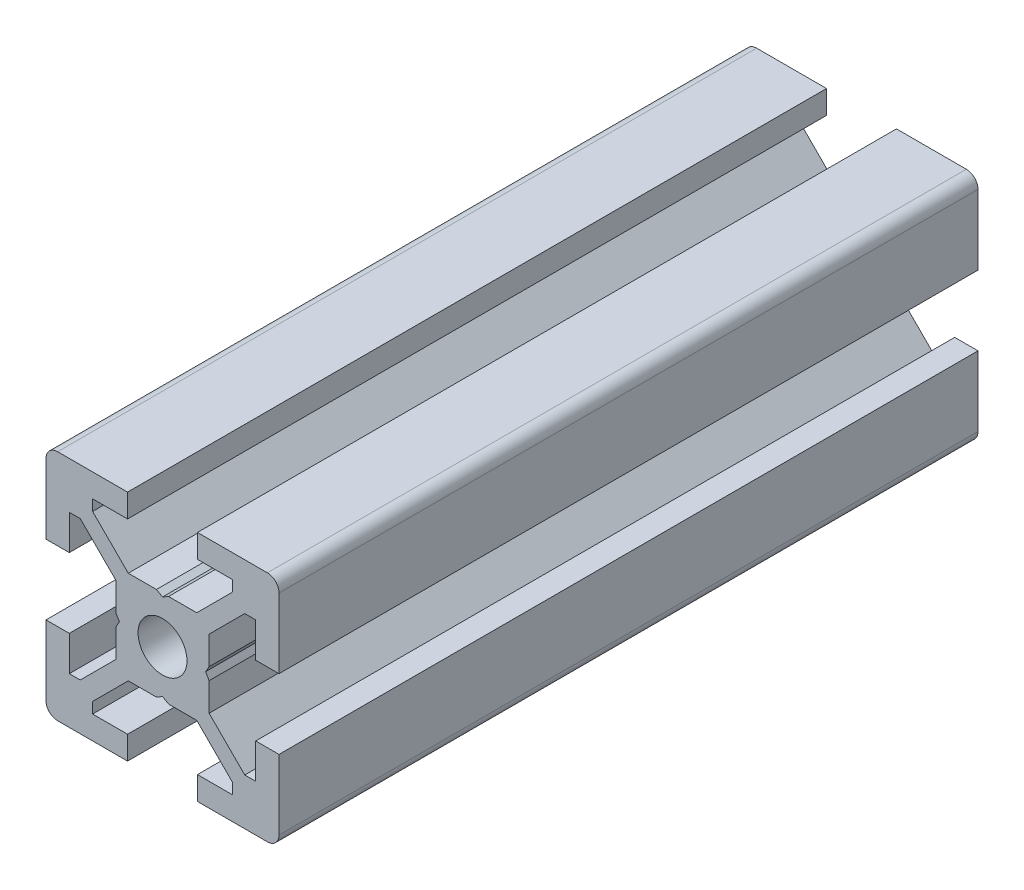
SolidWorks part; units mm, degrees
ref_plane "Front Plane" through (0, 0, 0) normal (0, 0, 1) x (1, 0, 0)
ref_plane "Top Plane" through (0, 0, 0) normal (0, 1, 0) x (1, 0, 0)
ref_plane "Right Plane" through (0, 0, 0) normal (1, 0, 0) x (0, 0, -1)
ref_plane "Plane1" through (0, 0, 0) normal (0, 0, 1) x (1, 0, 0)
sketch "Sketch1" plane through (0, 0, 0) normal (0, 0, 1) x (1, 0, 0)
  line L0 (-10, -3) -> (-10, -9)
  line L1 (-9, -10) -> (-3, -10)
  line L2 (-3, -10) -> (-3, -8)
  line L3 (-3, -8) -> (-6, -8)
  line L4 (-6, -8) -> (-6, -7.0607)
  line L5 (-6, -7.0607) -> (-2.9393, -4)
  line L6 (-2.9393, -4) -> (-0.5196, -4)
  line L7 (-0.5196, -4) -> (0, -3.7)
  line L8 (0, -3.7) -> (0.5196, -4)
  line L9 (0.5196, -4) -> (2.9393, -4)
  line L10 (2.9393, -4) -> (6, -7.0607)
  line L11 (6, -7.0607) -> (6, -8)
  line L12 (6, -8) -> (3, -8)
  line L13 (3, -8) -> (3, -10)
  line L14 (3, -10) -> (9, -10)
  line L15 (10, -9) -> (10, -3)
  line L16 (10, -3) -> (8, -3)
  line L17 (8, -3) -> (8, -6)
  line L18 (8, -6) -> (7.0607, -6)
  line L19 (7.0607, -6) -> (4, -2.9393)
  line L20 (4, -2.9393) -> (4, -0.5196)
  line L21 (4, -0.5196) -> (3.7, 0)
  line L22 (3.7, 0) -> (4, 0.5196)
  line L23 (4, 0.5196) -> (4, 2.9393)
  line L24 (4, 2.9393) -> (7.0607, 6)
  line L25 (7.0607, 6) -> (8, 6)
  line L26 (8, 6) -> (8, 3)
  line L27 (8, 3) -> (10, 3)
  line L28 (10, 3) -> (10, 9)
  line L29 (9, 10) -> (3, 10)
  line L30 (3, 10) -> (3, 8)
  line L31 (3, 8) -> (6, 8)
  line L32 (6, 8) -> (6, 7.0607)
  line L33 (6, 7.0607) -> (2.9393, 4)
  line L34 (2.9393, 4) -> (0.5196, 4)
  line L35 (0.5196, 4) -> (0, 3.7)
  line L36 (0, 3.7) -> (-0.5196, 4)
  line L37 (-0.5196, 4) -> (-2.9393, 4)
  line L38 (-2.9393, 4) -> (-6, 7.0607)
  line L39 (-6, 7.0607) -> (-6, 8)
  line L40 (-6, 8) -> (-3, 8)
  line L41 (-3, 8) -> (-3, 10)
  line L42 (-3, 10) -> (-9, 10)
  line L43 (-10, 9) -> (-10, 3)
  line L44 (-10, 3) -> (-8, 3)
  line L45 (-8, 3) -> (-8, 6)
  line L46 (-8, 6) -> (-7.0607, 6)
  line L47 (-7.0607, 6) -> (-4, 2.9393)
  line L48 (-4, 2.9393) -> (-4, 0.5196)
  line L49 (-4, 0.5196) -> (-3.7, 0)
  line L50 (-3.7, 0) -> (-4, -0.5196)
  line L51 (-4, -0.5196) -> (-4, -2.9393)
  line L52 (-4, -2.9393) -> (-7.0607, -6)
  line L53 (-7.0607, -6) -> (-8, -6)
  line L54 (-8, -6) -> (-8, -3)
  line L55 (-8, -3) -> (-10, -3)
  arc A0 (-10, -9) -> (-9, -10) centre (-9, -9) ccw
  arc A1 (9, -10) -> (10, -9) centre (9, -9) ccw
  arc A2 (10, 9) -> (9, 10) centre (9, 9) ccw
  arc A3 (-9, 10) -> (-10, 9) centre (-9, 9) ccw
extrude "Boss-Extrude1" add sketch "Sketch1" against normal blind 60
ref_plane "Plane2" through (0, 0, 0) normal (1, 0, 0) x (0, 0, -1)
sketch "Sketch2" plane through (0, 0, 0) normal (1, 0, 0) x (0, 0, -1)
  line L0 (0, 0) -> (0, 2.1)
  line L1 (0, 2.1) -> (60, 2.1)
  line L2 (60, 2.1) -> (60, 0)
  line L3 (60, 0) -> (0, 0)
  line L4 (60, 0) -> (0, 0) construction
revolve "Cut-Revolve1" cut sketch "Sketch2" angle 360 about L4 reverse direction yes
